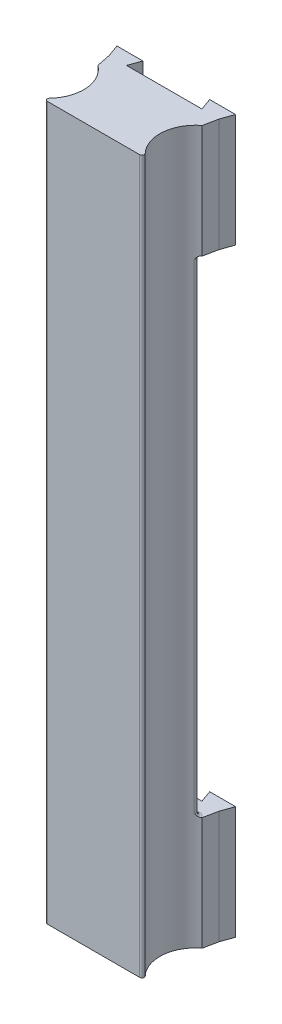
SolidWorks part; units mm, degrees
material "ABS"
ref_plane "Front" through (0, 0, 0) normal (0, 0, 1) x (1, 0, 0)
ref_plane "Top" through (0, 0, 0) normal (0, 1, 0) x (1, 0, 0)
ref_plane "Right" through (0, 0, 0) normal (1, 0, 0) x (0, 0, -1)
sketch "Sketch1" plane through (0, 0, 0) normal (0, 1, 0) x (1, 0, 0)
  line L0 (-4.085, -2.5) -> (4.085, -2.5)
  line L1 (4.6084, 2.5) -> (-4.6084, 2.5) construction
  line L2 (0, 2.5) -> (0, -2.5) construction
  line L3 (-6.5, 0) -> (6.5, 0) construction
  line L7 (-5.1, 3.6659) -> (-5.6, 5.0659) construction
  line L8 (-5.6, 5.0659) -> (-2.6, 5.0659) construction
  line L9 (-2.6, 5.0659) -> (-3.1, 3.6659) construction
  line L10 (3.1, 3.6659) -> (2.6, 5.0659) construction
  line L11 (2.6, 5.0659) -> (5.6, 5.0659) construction
  line L12 (5.6, 5.0659) -> (5.1, 3.6659) construction
  line L13 (-2.6, 5.0659) -> (2.6, 5.0659) construction
  line L14 (3.1, 3.6659) -> (5.1, 3.6659) construction
  line L15 (-5.1, 3.6659) -> (-3.1, 3.6659) construction
  line L21 (3.3354, 3.75) -> (2.9548, 4.8159)
  line L22 (2.9548, 4.8159) -> (5.2452, 4.8159)
  line L23 (5.2452, 4.8159) -> (4.8646, 3.75)
  line L24 (-4.8646, 3.75) -> (-5.2452, 4.8159)
  line L25 (-5.2452, 4.8159) -> (-2.9548, 4.8159)
  line L26 (-2.9548, 4.8159) -> (-3.3354, 3.75)
  line L27 (4.6084, 2.5) -> (4.8646, 3.75)
  line L28 (-4.6084, 2.5) -> (-4.8646, 3.75)
  line L29 (-3.3354, 3.75) -> (3.3354, 3.75)
  arc A0 (4.2298, -2.1621) -> (4.6084, 2.5) centre (6.5, 0) cw
  arc A1 (-4.6084, 2.5) -> (-4.2298, -2.1621) centre (-6.5, 0) cw
  arc A2 (4.085, -2.5) -> (4.2298, -2.1621) centre (4.085, -2.3) ccw
  arc A3 (-4.085, -2.5) -> (-4.2298, -2.1621) centre (-4.085, -2.3) cw
  point P17 (0, 5.0659)
  point P22 (-4.1, 3.6659)
  point P23 (-4.1, 5.0659)
  point P24 (4.1, 3.6659)
  point P25 (4.1, 5.0659)
  dimension "D1" = 3.135
  dimension "D3" = 5
  dimension "D11" = 0.2
  dimension "D2" = 13
  dimension "D4" = 1.25
  dimension "D5" = 3
  dimension "D6" = 3
  dimension "D7" = 2
  dimension "D8" = 2
  dimension "D9" = 1.4
  dimension "D10" = 6.2
  dimension "D12" = 0.25
extrude "Boss-Extrude2" add sketch "Sketch1" along normal mid plane 63 contours A1 A3 L0 A2 A0 L27 L23 L22 L21 L29 L26 L25 L24 L28
sketch "Sketch2" plane through (0, 0, 0) normal (1, 0, 0) x (0, 0, -1)
  line L1 (4.8159, 21.5) -> (2.5, 21.5)
  line L2 (4.8159, 21.5) -> (4.8159, -21.5)
  line L3 (4.8159, -21.5) -> (2.5, -21.5)
  line L4 (2.5, 21.5) -> (2.5, -21.5)
  line L5 (4.8159, 21.5) -> (2.5, -21.5) construction
  line L6 (4.8159, -21.5) -> (2.5, 21.5) construction
  line L11 (4.8159, 31.5) -> (4.8159, -31.5) construction
  line L12 (4.8159, 31.5) -> (3.75, 31.5) construction
  line L13 (2.5, 31.5) -> (2.5, -31.5) construction
  point P4 (3.658, 0)
  dimension "D1" = 10
extrude "Cut-Extrude1" cut sketch "Sketch2" against normal through all both and the other way through all
sketch "Sketch3" plane through (0, 0, 0) normal (0, 1, 0) x (1, 0, 0)
  line L0 (4.6084, 2.5) -> (4.085, 2.5)
  line L1 (-4.085, 2.5) -> (-4.6084, 2.5)
  arc A0 (4.6084, 2.5) -> (4.2298, 2.1621) centre (6.5, 0) ccw
  arc A1 (-4.6084, 2.5) -> (-4.2298, 2.1621) centre (-6.5, 0) cw
  arc A2 (4.6084, 2.5) -> (4.2298, -2.1621) centre (6.5, 0) ccw construction
  arc A3 (-4.2298, -2.1621) -> (-4.6084, 2.5) centre (-6.5, 0) ccw construction
  arc A4 (4.2298, 2.1621) -> (4.085, 2.5) centre (4.085, 2.3) ccw
  arc A5 (-4.085, 2.5) -> (-4.2298, 2.1621) centre (-4.085, 2.3) ccw
  dimension "D1" = 0.4
extrude "Cut-Extrude2" cut sketch "Sketch3" against normal up to surface (21.5 mm away) and the other way up to surface (21.5 mm away) up to face at (0, -21.5, -3.9264) other way up to face at (0, 21.5, -3.9264)
fillet "Fillet1" radius 0.3 6 edges at (0, -21.5, -2.5) (0, 21.5, -2.5) (-4.2688, -21.5, -2.3788) (4.2688, -21.5, -2.3788) (-4.2688, 21.5, -2.3788) (4.2688, 21.5, -2.3788)
